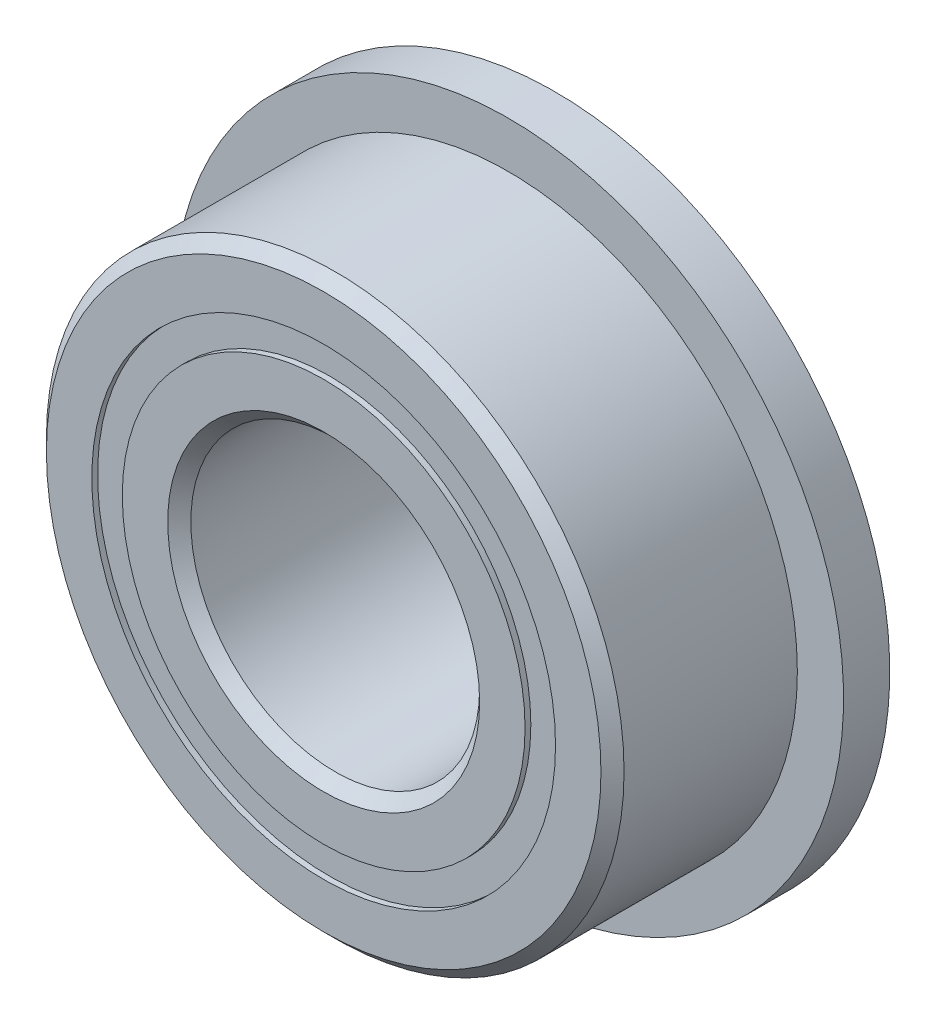
SolidWorks part; units mm, degrees
ref_plane "Front Plane" through (0, 0, 0) normal (0, 0, 1) x (1, 0, 0)
ref_plane "Top Plane" through (0, 0, 0) normal (0, 1, 0) x (1, 0, 0)
ref_plane "Right Plane" through (0, 0, 0) normal (1, 0, 0) x (0, 0, -1)
sketch "Sketch1" plane through (0, 0, 0) normal (1, 0, 0) x (0, 0, -1)
  line L0 (-2, 0) -> (2, 0) construction
  line L1 (0, 5) -> (0, -5) construction
  line L2 (1.8, 5) -> (-1.8, 5)
  line L3 (-1.8, 5) -> (-2, 4.8)
  line L4 (-2, 4.8) -> (-2, 4.0137)
  line L5 (-2, 4.0137) -> (-0.8889, 4.0137)
  line L6 (2, 4.0137) -> (0.8889, 4.0137)
  line L7 (2, 4.8) -> (2, 4.0137)
  line L8 (1.8, 5) -> (2, 4.8)
  line L9 (0, 5) -> (0, 3.75) construction
  line L10 (0, 3.75) -> (0, 2.5) construction
  arc A0 (-0.8889, 4.0137) -> (0.8889, 4.0137) centre (0, 3.75) cw
  point P14 (0, 2.5)
  dimension "D3" = 1.7778
  dimension "D1" = 45
  dimension "Width" = 4
  dimension "OD" = 10
  dimension "D2" = 0.2
  dimension "Shaft Dia" = 5
  dimension "D4" = 0.2637
revolve "Revolve1" add sketch "Sketch1" angle 360 about L0
sketch "Sketch3" plane through (0, 0, 0) normal (1, 0, 0) x (0, 0, -1)
  line L0 (-2, 3.4863) -> (-0.8889, 3.4863)
  line L1 (0, 5) -> (0, -5) construction
  line L2 (-2, 4.8) -> (-2, 4.0137) construction
  line L3 (-2, 3.4863) -> (-2, 2.7)
  line L4 (-1.8, 5) -> (-2, 4.8) construction
  line L5 (-2, 2.7) -> (-1.8, 2.5)
  line L6 (-1.8, 2.5) -> (1.8, 2.5)
  line L7 (1.8, 5) -> (1.8, -5) construction
  line L8 (1.8, 2.5) -> (2, 2.7)
  line L9 (2, -4.8) -> (2, 4.8) construction
  line L10 (2, 2.7) -> (2, 3.4863)
  line L11 (2, 3.4863) -> (0.8889, 3.4863)
  line L13 (1.8, 5) -> (2, 4.8) construction
  arc A0 (0.8889, 4.0137) -> (-0.8889, 4.0137) centre (0, 3.75) ccw construction
  arc A1 (0.8889, 3.4863) -> (-0.8889, 3.4863) centre (0, 3.75) cw
revolve "Revolve3" add sketch "Sketch3" angle 360 about L0
sketch "Sketch4" plane through (0, 0, 0) normal (1, 0, 0) x (0, 0, -1)
  line L0 (-0.9272, 3.75) -> (0.9272, 3.75)
  arc A2 (-0.9272, 3.75) -> (0.9272, 3.75) centre (0, 3.75) cw
  arc A3 (0.8889, 4.0137) -> (-0.8889, 4.0137) centre (0, 3.75) ccw construction
revolve "Revolve4" add sketch "Sketch4" angle 360 about L0
ref_axis "Axis1" through (0, 0, -2) along (0, 0, 1)
pattern_circular "CirPattern1" count 12 every 30 about axis through (0, 0, -2) along (0, 0, 1) of bodies 104
sketch "Sketch5" plane through (0, 0, 0) normal (1, 0, 0) x (0, 0, -1)
  line L0 (-2, 4.0137) -> (-0.8889, 4.0137) construction
  line L1 (-1.9, 4.0137) -> (-0.9272, 4.0137)
  line L2 (-1.9, 4.0137) -> (-1.9, 3.4863)
  line L3 (-1.9, 3.4863) -> (-0.9272, 3.4863)
  line L4 (-0.9272, 4.0137) -> (-0.9272, 3.4863)
  line L5 (-2, 3.4863) -> (-0.8889, 3.4863) construction
  line L6 (2, 4.0137) -> (0.8889, 4.0137) construction
  line L7 (1.9, 4.0137) -> (0.9272, 4.0137)
  line L8 (1.9, 4.0137) -> (1.9, 3.4863)
  line L9 (1.9, 3.4863) -> (0.9272, 3.4863)
  line L10 (0.9272, 4.0137) -> (0.9272, 3.4863)
  line L11 (2, 3.4863) -> (0.8889, 3.4863) construction
  line L12 (-1.8, 5) -> (-2, 4.8) construction
  point P18 (-1.9, 4.9)
revolve "Revolve5" add sketch "Sketch5" angle 360 about L0
sketch "Sketch6" plane through (0, 0, 0) normal (1, 0, 0) x (0, 0, -1)
  line L0 (2, 0) -> (-2, 0) construction
  line L1 (2, 4.0137) -> (1.2, 4.0137)
  line L2 (2, 4.0137) -> (2, 5.8)
  line L3 (2, 5.8) -> (1.2, 5.8)
  line L4 (1.2, 4.0137) -> (1.2, 5.8)
  dimension "Th" = 0.8
  dimension "Flange OD" = 11.6
revolve "Revolve6" add sketch "Sketch6" angle 360 about L0
equation "\"D2@Sketch1\" = \"Width@Sketch1\"*.05"
equation "\"D3@Sketch1\" = \"Width@Sketch1\"/2.25"
equation "\"D4@Sketch1\" = (((\"OD@Sketch1\"-\"Width@Sketch1\")/2)/3.25)/3.5"
equation "\"D2@CirPattern1\" = 360/\"Balls@CirPattern1\""
